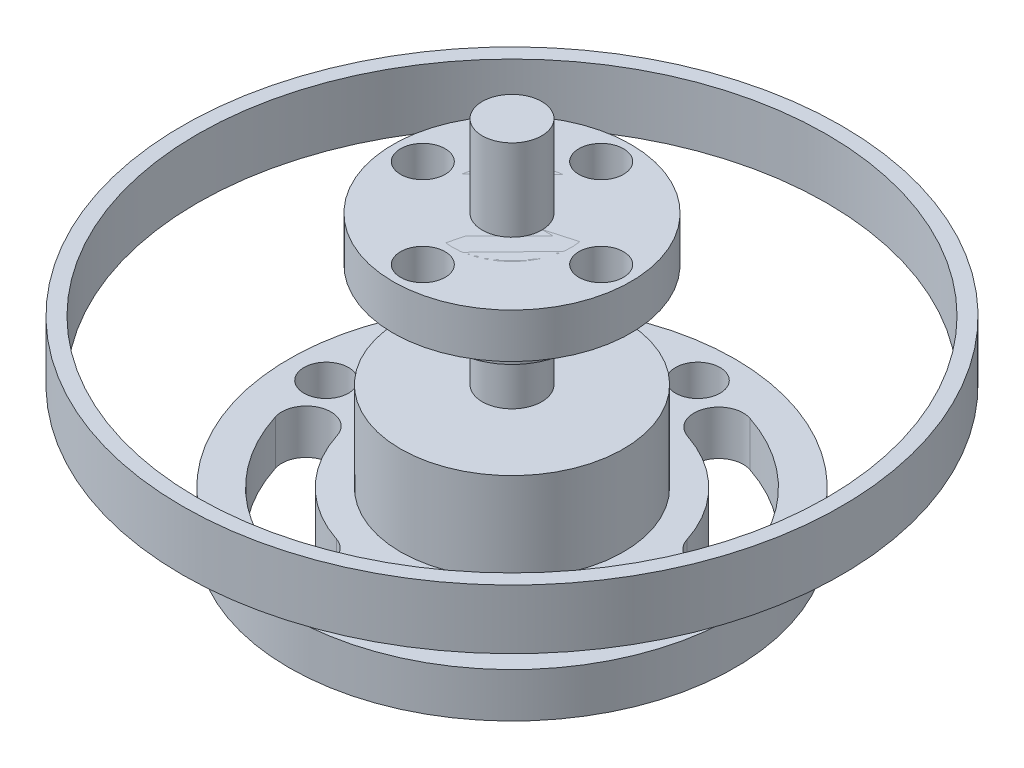
SolidWorks part; units mm, degrees
ref_plane "Front Plane" through (0, 0, 0) normal (0, 0, 1) x (1, 0, 0)
ref_plane "Top Plane" through (0, 0, 0) normal (0, 1, 0) x (1, 0, 0)
ref_plane "Right Plane" through (0, 0, 0) normal (1, 0, 0) x (0, 0, -1)
sketch "Sketch1" plane through (0, 0, 0) normal (0, 1, 0) x (1, 0, 0)
  circle A0 centre (0, 0) radius 2
  circle A1 centre (0, 0) radius 15
  circle A3 centre (0, 12.5) radius 1.5
  circle A4 centre (12.5, 0) radius 1.5
  circle A5 centre (0, -12.5) radius 1.5
  circle A6 centre (-12.5, 0) radius 1.5
  circle A8 centre (0, 0) radius 5.6886
  arc A9 (-10.474, 3.4326) -> (-3.335, 10.5055) centre (0, 0) cw construction
  arc A14 (-3.8366, 12.0853) -> (-12.0491, 3.9488) centre (0, 0) ccw
  arc A15 (-2.8335, 8.9256) -> (-8.8989, 2.9164) centre (0, 0) ccw
  arc A16 (-2.8335, 8.9256) -> (-3.8366, 12.0853) centre (-3.335, 10.5055) ccw
  arc A17 (-12.0491, 3.9488) -> (-8.8989, 2.9164) centre (-10.474, 3.4326) ccw
  arc A18 (3.4326, 10.474) -> (10.5055, 3.335) centre (0, 0) cw construction
  arc A19 (12.0853, 3.8366) -> (3.9488, 12.0491) centre (0, 0) ccw
  arc A20 (8.9256, 2.8335) -> (2.9164, 8.8989) centre (0, 0) ccw
  arc A21 (8.9256, 2.8335) -> (12.0853, 3.8366) centre (10.5055, 3.335) ccw
  arc A22 (3.9488, 12.0491) -> (2.9164, 8.8989) centre (3.4326, 10.474) ccw
  arc A23 (10.474, -3.4326) -> (3.335, -10.5055) centre (0, 0) cw construction
  arc A24 (3.8366, -12.0853) -> (12.0491, -3.9488) centre (0, 0) ccw
  arc A25 (2.8335, -8.9256) -> (8.8989, -2.9164) centre (0, 0) ccw
  arc A26 (2.8335, -8.9256) -> (3.8366, -12.0853) centre (3.335, -10.5055) ccw
  arc A27 (12.0491, -3.9488) -> (8.8989, -2.9164) centre (10.474, -3.4326) ccw
  arc A28 (-3.4326, -10.474) -> (-10.5055, -3.335) centre (0, 0) cw construction
  arc A29 (-12.0853, -3.8366) -> (-3.9488, -12.0491) centre (0, 0) ccw
  arc A30 (-8.9256, -2.8335) -> (-2.9164, -8.8989) centre (0, 0) ccw
  arc A31 (-8.9256, -2.8335) -> (-12.0853, -3.8366) centre (-10.5055, -3.335) ccw
  arc A32 (-3.9488, -12.0491) -> (-2.9164, -8.8989) centre (-3.4326, -10.474) ccw
  circle A33 centre (0, 0) radius 7.5
  point P9 (-7.7575, 7.83)
  point P16 (0, 0)
  point P26 (7.83, 7.7575)
  point P33 (7.7575, -7.83)
  point P40 (-7.83, -7.7575)
  point P45 (0, 0)
  dimension "D1" = 4
  dimension "D2" = 4
extrude "Boss-Extrude3" add sketch "Sketch1" along normal blind 24.5 and the other way blind 2.5 contours A0 region at (0, 0, 0)
extrude "Boss-Extrude4" add sketch "Sketch1<6>" along normal blind 9 separate body contours A33 A8 | A8 region at (-7.2879, 0, 0)
sketch "Sketch1<6>" plane through (0, 0, 0) normal (0, 1, 0) x (1, 0, 0) same geometry as "Sketch1"
extrude "Boss-Extrude5" add sketch "Sketch1<8>" along normal blind 3 contours A1 A33 A32 A29 A31 A30 A27 A24 A26 A25 A22 A19 A21 A20 A17 A14 A16 A15 A6 A5 A4 A3 region at (-14.5757, 0, 0)
sketch "Sketch1<8>" plane through (0, 0, 0) normal (0, 1, 0) x (1, 0, 0) same geometry as "Sketch1"
sketch "Sketch3" plane through (0, 9, 0) normal (0, 1, 0) x (1, 0, 0)
  circle A0 centre (0, 0) radius 22.175
  circle A1 centre (0, 0) radius 21.175
extrude "Boss-Extrude6" add sketch "Sketch3" along normal blind 4
sketch "Sketch4" plane through (0, 13, 0) normal (0, 1, 0) x (1, 0, 0)
  circle A0 centre (0, 0) radius 4
extrude "Boss-Extrude7" add sketch "Sketch4" along normal blind 6
sketch "Sketch5" plane through (0, 19, 0) normal (0, 1, 0) x (1, 0, 0)
  circle A1 centre (0, 0) radius 6
  circle A2 centre (0, 0) radius 8
  circle A3 centre (-6, 0) radius 1.5
  circle A4 centre (0, 6) radius 1.5
  circle A5 centre (6, 0) radius 1.5
  circle A6 centre (0, -6) radius 1.5
  point P16 (0, 0)
  dimension "D1" = 4
extrude "Boss-Extrude8" add sketch "Sketch5" against normal blind 3 separate body contours A2 | A5 | A4 | A6 | A3
